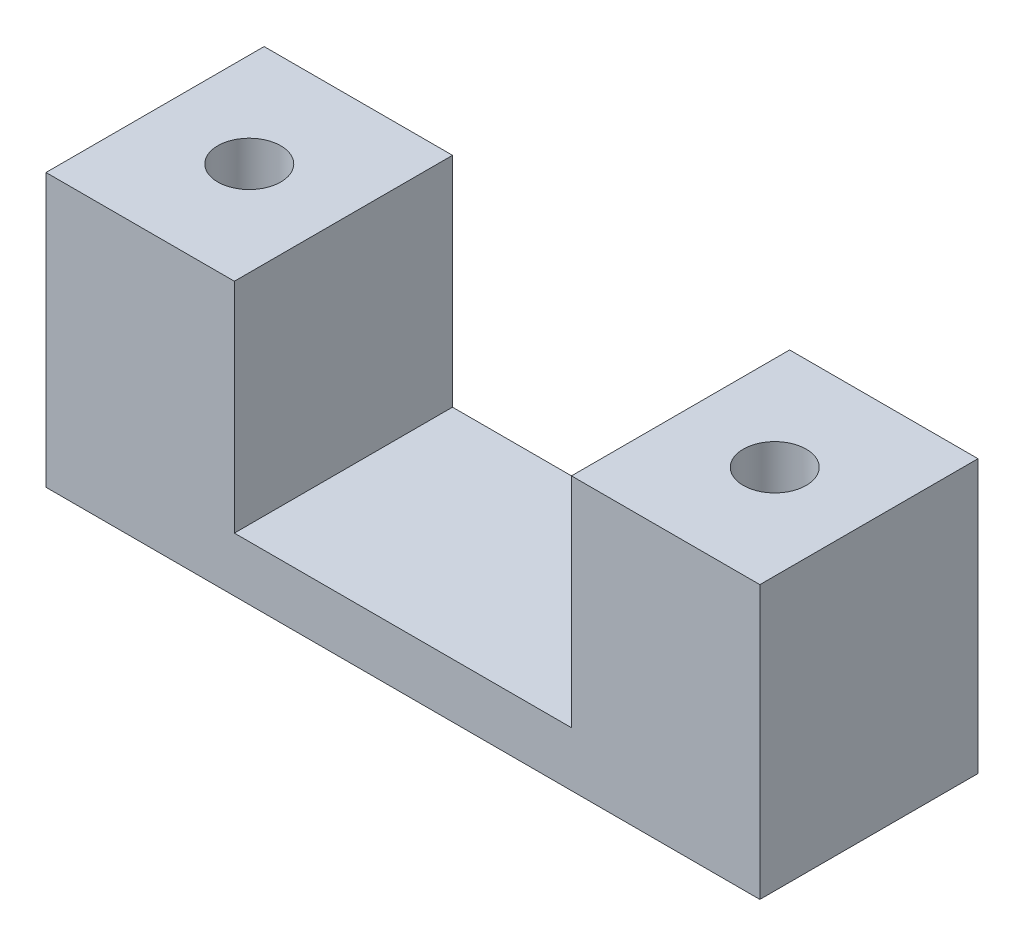
SolidWorks part; units mm, degrees
ref_plane "Front Plane" through (0, 0, 0) normal (0, 0, 1) x (1, 0, 0)
ref_plane "Top Plane" through (0, 0, 0) normal (0, 1, 0) x (1, 0, 0)
ref_plane "Right Plane" through (0, 0, 0) normal (1, 0, 0) x (0, 0, -1)
sketch "Sketch1" plane through (0, 0, 0) normal (0, 1, 0) x (1, 0, 0)
  line L1 (0, 0) -> (72, 0)
  line L2 (0, 0) -> (0, 22)
  line L3 (0, 22) -> (72, 22)
  line L4 (72, 0) -> (72, 22)
  line L7 (30.2143, -18.8036) -> (29.5714, -18.8036)
  dimension "D1" = 72
  dimension "D2" = 22
extrude "Boss-Extrude1" add sketch "Sketch1" along normal blind 27.5 contours L1 L4 L3 L2 region at (36, 0, -11)
sketch "Sketch2" plane through (0, 27.5, 0) normal (0, 1, 0) x (1, 0, 0)
  line L0 (0, 0) -> (72, 0) construction
  line L1 (19, 22) -> (53, 22)
  line L2 (19, 22) -> (19, 0)
  line L3 (19, 0) -> (53, 0)
  line L4 (53, 22) -> (53, 0)
  line L5 (19, 22) -> (53, 0) construction
  line L6 (19, 0) -> (53, 22) construction
  line L7 (36, 0) -> (36, 11) construction
  point P0 (36, 11)
  dimension "D1" = 34
  dimension "D2" = 22
extrude "Cut-Extrude1" cut sketch "Sketch2" against normal blind 22
sketch "Sketch3" plane through (0, 27.5, 0) normal (0, 1, 0) x (1, 0, 0)
  line L0 (36, 22) -> (36, 0) construction
  line L1 (53, 22) -> (19, 22) construction
  line L2 (19, 0) -> (53, 0) construction
  line L3 (19, 22) -> (19, 0) construction
  circle A0 centre (9.5, 11) radius 3.175
  circle A1 centre (62.5, 11) radius 3.175
  dimension "D1" = 6.35
  dimension "D2" = 9.5
extrude "Cut-Extrude2" cut sketch "Sketch3" against normal blind 69
sketch "Sketch5" plane through (0, 0, 0) normal (0, -1, 0) x (1, 0, 0)
  line L0 (36, 0) -> (36, -22) construction
  line L1 (0, 0) -> (72, 0) construction
  line L2 (0, -22) -> (72, -22) construction
  circle A0 centre (9.5, -11) radius 5.5
  circle A1 centre (62.5, -11) radius 5.5
  dimension "D1" = 11
extrude "Cut-Extrude3" cut sketch "Sketch5" against normal blind 5.5
sketch "Sketch4" plane through (0, 27.5, 0) normal (0, 1, 0) x (1, 0, 0)
  line L0 (36, 22) -> (36, 0) construction
  line L1 (9.5, 17) -> (4.3038, 14)
  line L2 (4.3038, 14) -> (4.3038, 8)
  line L3 (4.3038, 8) -> (9.5, 5)
  line L4 (9.5, 5) -> (14.6962, 8)
  line L5 (14.6962, 8) -> (14.6962, 14)
  line L6 (14.6962, 14) -> (9.5, 17)
  line L7 (53, 22) -> (19, 22) construction
  line L8 (19, 0) -> (53, 0) construction
  line L9 (57.3038, 14) -> (62.5, 17)
  line L10 (57.3038, 8) -> (57.3038, 14)
  line L11 (62.5, 5) -> (57.3038, 8)
  line L12 (67.6962, 8) -> (62.5, 5)
  line L13 (67.6962, 14) -> (67.6962, 8)
  line L14 (62.5, 17) -> (67.6962, 14)
  circle A0 centre (9.5, 11) radius 5.1962 construction
  circle A1 centre (62.5, 11) radius 5.1962 construction
  circle A2 centre (62.5, 11) radius 7.5
  circle A3 centre (9.5, 11) radius 8.7677
  dimension "D2" = 15
  dimension "D1" = 6
